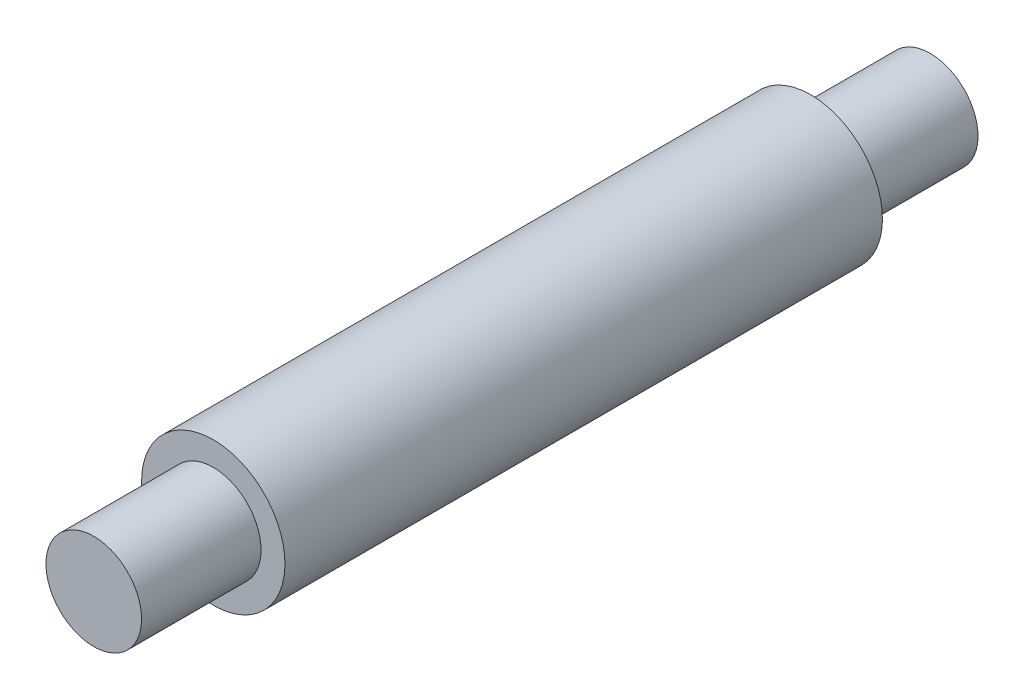
SolidWorks part; units mm, degrees
material "Plain Carbon Steel"
ref_plane "Front Plane" through (0, 0, 0) normal (0, 0, 1) x (1, 0, 0)
ref_plane "Top Plane" through (0, 0, 0) normal (0, 1, 0) x (1, 0, 0)
ref_plane "Right Plane" through (0, 0, 0) normal (1, 0, 0) x (0, 0, -1)
sketch "Sketch1" plane through (0, 0, 0) normal (1, 0, 0) x (0, 0, -1)
  line L0 (-10, 0) -> (-10, 4)
  line L1 (-10, 4) -> (0, 4)
  line L2 (0, 4) -> (0, 6)
  line L3 (0, 6) -> (50, 6)
  line L4 (50, 6) -> (50, 4)
  line L5 (50, 4) -> (60, 4)
  line L6 (60, 4) -> (60, 0)
  line L7 (60, 0) -> (-10, 0)
  dimension "D1" = 50
  dimension "D2" = 6
  dimension "D3" = 4
  dimension "D4" = 10
revolve "Revolve1" add sketch "Sketch1" angle 360 about L7
